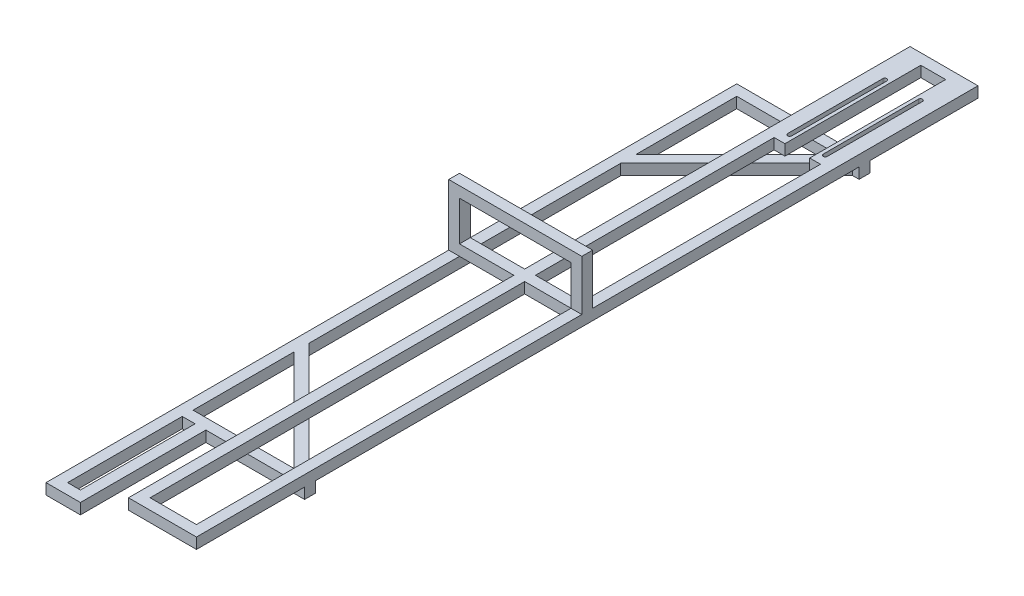
SolidWorks part; units mm, degrees
ref_plane "Front Plane" through (0, 0, 0) normal (0, 0, 1) x (1, 0, 0)
ref_plane "Top Plane" through (0, 0, 0) normal (0, 1, 0) x (1, 0, 0)
ref_plane "Right Plane" through (0, 0, 0) normal (1, 0, 0) x (0, 0, -1)
sketch "Sketch1" plane through (0, 0, 0) normal (0, 1, 0) x (1, 0, 0)
  line L1 (-50, 575) -> (50, 575)
  line L2 (-50, 575) -> (-50, -575)
  line L3 (-50, -575) -> (50, -575)
  line L4 (50, 575) -> (50, -575)
  line L8 (-34.125, 559.125) -> (34.125, 559.125)
  line L9 (34.125, 559.125) -> (34.125, -559.125)
  line L10 (-34.125, -559.125) -> (34.125, -559.125)
  line L11 (-34.125, 559.125) -> (-34.125, -559.125)
  point P4 (0, 575)
  point P6 (50, 0)
  dimension "D1" = 100
  dimension "D2" = 1150
  dimension "D3" = 15.875
extrude "Boss-Extrude1" add sketch "Sketch1" along normal blind 15.875
sketch "Sketch3" plane through (0, 15.875, 0) normal (0, 1, 0) x (1, 0, 0)
  line L0 (-145.875, 558.625) -> (-145.875, -591.375) construction
  line L3 (34.125, 400) -> (-130, 400)
  line L4 (-130, 220.5939) -> (-130, 400)
  line L6 (50, 415.875) -> (-145.875, 415.875)
  line L7 (-145.875, 217.7568) -> (-145.875, 415.875)
  line L9 (50, 400) -> (50, 415.875)
  line L10 (-8.7312, 0) -> (8.7312, 0) construction
  line L11 (50, -400) -> (50, -415.875)
  line L13 (-145.875, 217.7568) -> (-145.875, -415.875)
  line L14 (50, -415.875) -> (-145.875, -415.875)
  line L15 (-130, 220.5939) -> (-130, -400)
  line L18 (34.125, -400) -> (-130, -400)
  line L19 (50, -575) -> (50, 575) construction
  line L20 (50, -312.7388) -> (-145.875, 217.7568) construction
  line L21 (34.125, -223.912) -> (-130, 220.5939) construction
  line L22 (34.125, 400) -> (50, 400)
  line L23 (34.125, -400) -> (50, -400)
  line L25 (50, -312.7388) -> (50, 415.875) construction
  line L26 (34.125, -223.912) -> (34.125, 400) construction
  dimension "D1" = 400
  dimension "D3" = 15.875
extrude "Boss-Extrude2" add sketch "Sketch3" against normal blind 15.875 from surface starting at face at (0, 0, 0)
sketch "Sketch5" plane through (0, 0, 0) normal (0, 0, 1) x (1, 0, 0)
  line L0 (-145.875, 959.91) -> (-145.875, -15.875) construction
  line L1 (50, 0) -> (-145.875, 0)
  line L2 (50, 0) -> (50, 90)
  line L3 (50, 90) -> (-145.875, 90)
  line L4 (-145.875, 0) -> (-145.875, 90)
  line L5 (34.125, 74.125) -> (-130, 74.125)
  line L6 (-130, 15.875) -> (-130, 74.125)
  line L7 (34.125, 15.875) -> (-130, 15.875)
  line L8 (34.125, 15.875) -> (34.125, 74.125)
  dimension "D1" = 90
  dimension "D2" = 15.875
extrude "Boss-Extrude3" add sketch "Sketch5" along normal mid plane 15.875
sketch "Sketch6" plane through (0, 0, 0) normal (0, -1, 0) x (1, 0, 0)
  line L6 (-34.125, -559.125) -> (-18.25, -559.125)
  line L7 (-34.125, -559.125) -> (-34.125, -359.125)
  line L8 (-34.125, -359.125) -> (-18.25, -359.125)
  line L9 (-18.25, -559.125) -> (-18.25, -359.125)
  line L10 (34.125, -559.125) -> (18.25, -559.125)
  line L11 (34.125, -559.125) -> (34.125, -359.125)
  line L12 (34.125, -359.125) -> (18.25, -359.125)
  line L13 (18.25, -559.125) -> (18.25, -359.125)
  line L14 (34.125, -559.125) -> (-34.125, -559.125) construction
  dimension "D1" = 15.875
  dimension "D2" = 15.875
  dimension "D4" = 200
extrude "Boss-Extrude4" add sketch "Sketch6" against normal blind 15.875
sketch "Sketch7" plane through (0, 0, 0) normal (0, -1, 0) x (1, 0, 0)
  line L0 (-26.1875, -374.125) -> (-26.1875, -514.125) construction
  line L1 (-23.1875, -374.125) -> (-23.1875, -514.125)
  line L2 (-29.1875, -374.125) -> (-29.1875, -514.125)
  line L3 (26.1875, -374.125) -> (26.1875, -514.125) construction
  line L4 (29.1875, -374.125) -> (29.1875, -514.125)
  line L5 (23.1875, -374.125) -> (23.1875, -514.125)
  line L6 (-18.25, -359.125) -> (-34.125, -359.125) construction
  line L7 (34.125, -359.125) -> (18.25, -359.125) construction
  arc A0 (-23.1875, -374.125) -> (-29.1875, -374.125) centre (-26.1875, -374.125) ccw
  arc A1 (-29.1875, -514.125) -> (-23.1875, -514.125) centre (-26.1875, -514.125) ccw
  arc A2 (29.1875, -374.125) -> (23.1875, -374.125) centre (26.1875, -374.125) ccw
  arc A3 (23.1875, -514.125) -> (29.1875, -514.125) centre (26.1875, -514.125) ccw
  point P2 (-26.1875, -444.125)
  point P7 (26.1875, -444.125)
  point P17 (-26.1875, -359.125)
  point P20 (26.1875, -359.125)
  dimension "D1" = 3
  dimension "D2" = 140
  dimension "D3" = 15
extrude "Cut-Extrude1" cut sketch "Sketch7" against normal blind 15.875
sketch "Sketch8" plane through (0, 0, 0) normal (0, 1, 0) x (1, 0, 0)
  line L1 (-95.25, -600.5) -> (-145.875, -600.5)
  line L2 (-95.25, -600.5) -> (-95.25, -400)
  line L3 (-95.25, -400) -> (-145.875, -400)
  line L4 (-145.875, -600.5) -> (-145.875, -400)
  line L5 (-130, -400) -> (-50, -400) construction
  line L6 (-111.125, -415.875) -> (-130, -415.875)
  line L7 (-130, -584.625) -> (-130, -415.875)
  line L8 (-111.125, -584.625) -> (-130, -584.625)
  line L9 (-111.125, -584.625) -> (-111.125, -415.875)
  line L10 (-145.875, -7.9375) -> (-145.875, -415.875) construction
  line L12 (-130, -590.5) -> (-145.875, -590.5) construction
  point P5 (-145.875, -400)
  point P7 (-97.9375, -400)
  point P17 (-137.9375, -590.5)
  dimension "D2" = 10
  dimension "D3" = 50.625
  dimension "D1" = 15.875
extrude "Boss-Extrude5" add sketch "Sketch8" against normal blind 15.875
sketch "Sketch9" plane through (0, 0, 0) normal (0, 1, 0) x (1, 0, 0)
  line L0 (45.3503, -404.6497) -> (34.125, -415.875)
  line L1 (45.3503, -404.6497) -> (-134.6497, -224.6497)
  line L2 (34.125, -415.875) -> (-145.875, -235.875)
  line L3 (-134.6497, -224.6497) -> (-145.875, -235.875)
  line L5 (34.125, -559.125) -> (34.125, -7.9375) construction
  line L6 (-34.125, -415.875) -> (34.125, -415.875) construction
  line L8 (-34.125, -400) -> (34.125, -400) construction
  line L10 (-145.875, 558.625) -> (-145.875, -591.375) construction
  point P10 (0, 0)
  point P11 (0, 0)
  point P12 (-199.6063, -199.5939)
  dimension "D1" = 15.875
  dimension "D2" = 45
extrude "Boss-Extrude6" add sketch "Sketch9" against normal blind 15.875
mirror "Mirror1" about plane through (0, 0, 0) normal (0, 0, 1) of "Boss-Extrude6"
